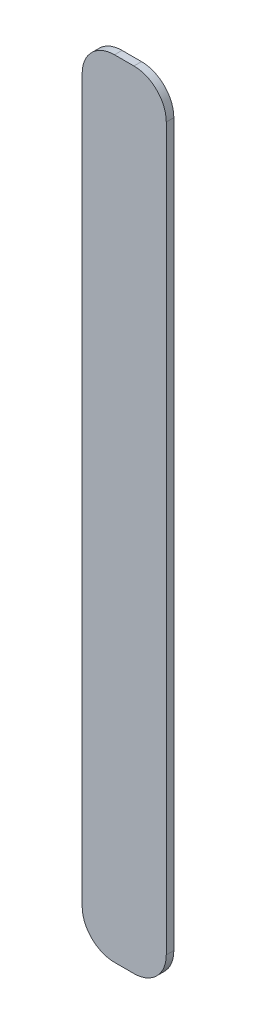
SolidWorks part; units mm, degrees
ref_plane "Front Plane" through (0, 0, 0) normal (0, 0, 1) x (1, 0, 0)
ref_plane "Top Plane" through (0, 0, 0) normal (0, 1, 0) x (1, 0, 0)
ref_plane "Right Plane" through (0, 0, 0) normal (1, 0, 0) x (0, 0, -1)
sketch "Sketch1" plane through (0, 0, 0) normal (0, 0, 1) x (1, 0, 0)
  line L0 (13, 13) -> (13, 91.5) construction
  line L1 (0, 0) -> (13, 0)
  line L2 (0, 0) -> (0, 121.5)
  line L3 (0, 121.5) -> (13, 121.5)
  line L4 (13, 0) -> (13, 121.5)
  line L5 (80.065, 121.5) -> (-49.585, 121.5) construction
base flange "Base-Flange1" sketch "Sketch1" thickness 1.17 reverse thickness direction no parameters "D1"=1.65
fillet "Fillet1" radius 5 4 edges at (0, 121.5, -0.585) (0, 0, -0.585) (13, 0, -0.585) (13, 121.5, -0.585)
sketch "Bend-Lines1" [suppressed] plane through (0, 0, 0) normal (0, 1, 0) x (1, 0, 0)
sketch "Bounding-Box1" [suppressed] plane through (0, 0, 0) normal (0, 1, 0) x (1, 0, 0)
sheet metal parameters "Sheet-Metal1" thickness 1.17 parameters "D1"=1.65
flat pattern "Flat-Pattern1" [suppressed]
sketch "Bend-Lines2" plane through (0, 0, 0) normal (0, 1, 0) x (1, 0, 0)
sketch3d "Bounding-Box2" [suppressed]
  line L0 (13, 0, 0) -> (13, 121.5, 0) construction
  line L1 (0, 0, 0) -> (0, 121.5, 0) construction
  line L2 (13, 0, 0) -> (0, 0, 0) construction
  line L3 (13, 121.5, 0) -> (0, 121.5, 0) construction
